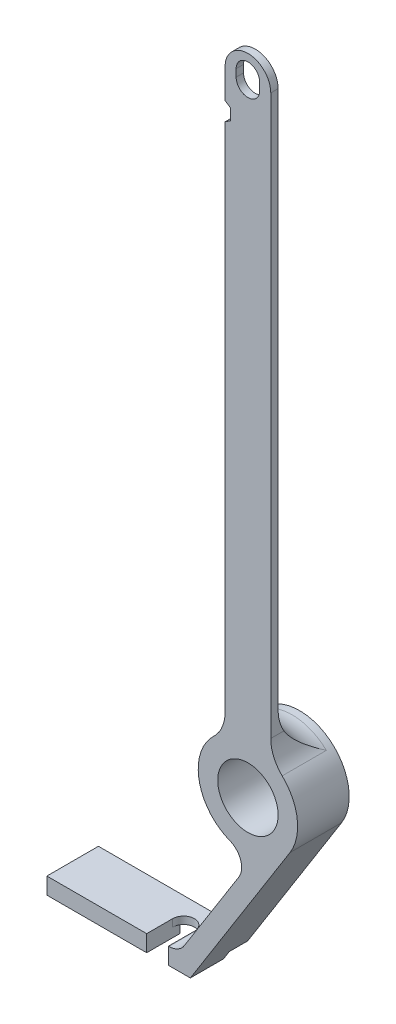
SolidWorks part; units mm, degrees
ref_plane "Front Plane" through (0, 0, 0) normal (0, 0, 1) x (1, 0, 0)
ref_plane "Top Plane" through (0, 0, 0) normal (0, 1, 0) x (1, 0, 0)
ref_plane "Right Plane" through (0, 0, 0) normal (1, 0, 0) x (0, 0, -1)
sketch "Sketch1" plane through (0, 0, 0) normal (0, 0, 1) x (1, 0, 0)
  line L0 (329.4964, 72.6482) -> (279.2958, 72.6482) construction
  line L1 (329.4964, 72.6482) -> (279.2958, 72.6482)
  line L2 (356.876, 116.1922) -> (329.4964, 72.6482)
  line L3 (279.2958, 72.6482) -> (279.2958, 77.6482)
  line L4 (279.2958, 77.6482) -> (326.7341, 77.6482)
  line L5 (347.0604, 109.9749) -> (326.7341, 77.6482)
  circle A2 centre (345.4475, 123.3782) radius 10.7
  circle A3 centre (345.4475, 123.3782) radius 10.7
  circle A5 centre (345.4475, 123.3782) radius 13.5
  circle A6 centre (345.4475, 123.3782) radius 13.5
  point P11 (321.6004, 79.1906)
  dimension "D3" = 5
  dimension "D4" = 5
  dimension "D1" = 0.2
  dimension "D2" = 3
extrude "Boss-Extrude1" add sketch "Sketch1" along normal blind 14 contours A6 L5 L4 L3 L1 L2 | A6 A3 region at (304.3961, 73.5378, 0) region at (352.467, 112.2961, 0)
sketch "Sketch2" plane through (0, 0, 14) normal (0, 0, 1) x (1, 0, 0)
  circle A1 centre (345.4475, 292.2362) radius 6.2
  arc A2 (348.6475, 292.2362) -> (345.3138, 289.039) centre (345.4475, 292.2362) ccw
  circle A3 centre (345.4475, 292.2362) radius 3.2
  point P0 (345.3789, 289.039)
  dimension "D1" = 0.2
  dimension "D2" = 3
extrude "Boss-Extrude2" add sketch "Sketch2" against normal blind 2 separate body
sketch "Sketch3" plane through (0, 0, 14) normal (0, 0, 1) x (1, 0, 0)
  line L0 (339.2475, 292.2362) -> (339.2475, 135.3703)
  line L1 (351.6475, 292.2362) -> (351.6475, 135.3703)
  line L2 (351.6475, 292.2362) -> (339.2475, 292.2362) construction
  circle A0 centre (345.4475, 292.2362) radius 6.2 construction
  arc A1 (356.876, 116.1922) -> (347.0604, 109.9749) centre (345.4475, 123.3782) ccw construction
  arc A2 (356.876, 116.1922) -> (347.0604, 109.9749) centre (345.4475, 123.3782) ccw
  circle A3 centre (345.4475, 292.2362) radius 6.2
  point P10 (339.307, 293.0933)
  circle M3 centre (345.4475, 292.2362) radius 6.2
extrude "Boss-Extrude3" add sketch "Sketch3" against normal blind 2 contours A2 L1 L0 M3 region at (345.4475, 211.8827, 14)
sketch "Sketch4" plane through (0, 0, 14) normal (0, 0, 1) x (1, 0, 0)
  line L0 (339.2475, 284.2362) -> (340.7475, 283.2362)
  line L1 (340.7475, 283.2362) -> (340.7475, 280.2362)
  line L2 (340.7475, 280.2362) -> (339.2475, 279.2362)
  line L3 (339.2475, 292.2362) -> (339.2475, 135.3703) construction
  line L4 (339.2475, 279.2362) -> (339.2475, 284.2362)
  circle A0 centre (345.4475, 292.2362) radius 3.2 construction
  point P2 (339.2475, 283.8537)
  dimension "D1" = 3
  dimension "D2" = 1.5
  dimension "D3" = 1
  dimension "D4" = 9
extrude "Cut-Extrude1" cut sketch "Sketch4" against normal blind 2
sketch "Sketch5" plane through (0, 77.6482, 0) normal (0, 1, 0) x (1, 0, 0)
  line L0 (284.9458, -6.9385) -> (284.9458, -16.0141)
  line L1 (284.9458, -16.0141) -> (290.8458, -16.0141)
  line L2 (290.8458, -16.0141) -> (290.8458, -6.9385)
  line L3 (317.9464, -6.9385) -> (317.9464, -18.3931)
  line L4 (317.9464, -18.3931) -> (323.8464, -18.3931)
  line L5 (323.8464, -18.3931) -> (323.8464, -6.9385)
  arc A2 (287.8958, -9.8885) -> (287.8958, -3.9885) centre (287.8958, -6.9385) ccw
  circle A3 centre (287.8958, -6.9385) radius 2.95
  arc A5 (320.8964, -9.8885) -> (320.8964, -3.9885) centre (320.8964, -6.9385) ccw
  circle A6 centre (320.8964, -6.9385) radius 2.95
  line M5 (279.2958, -14) -> (326.7341, -14)
  dimension "D1" = 0.2
  dimension "D2" = 0.2
extrude "Cut-Extrude2" cut sketch "Sketch5" against normal through all contours A6 L3 L5 M5 | A6 | A3 L0 L2 M5 | A3 region at (287.8958, 77.6482, 11.582) region at (320.8964, 77.6482, 11.582) region at (287.8958, 77.6482, 6.9385) region at (320.8964, 77.6482, 6.9385)
sketch "Sketch6" plane through (0, 0, 14) normal (0, 0, 1) x (1, 0, 0)
  circle A1 centre (345.4475, 123.3782) radius 10.7 construction
  circle A2 centre (345.4475, 123.3782) radius 8.2
  circle A3 centre (345.4475, 123.3782) radius 8.2
  circle A4 centre (345.4475, 123.3782) radius 10.7
  dimension "D1" = 0.2
extrude "Boss-Extrude4" add sketch "Sketch6" against normal blind 12.5
chamfer "Chamfer1" distance 1 angle 45 1 edges at (304.3961, 72.6482, 0)
fillet "Fillet1" radius 5 1 edges at (347.0604, 109.9749, 7)
fillet "Fillet2" radius 5 1 edges at (326.7341, 77.6482, 7)
fillet "Fillet3" radius 10 2 edges at (339.2475, 135.3703, 13) (351.6475, 135.3703, 13)
fillet "Fillet4" radius 10 1 edges at (345.4475, 136.8782, 12)
sketch "Sketch7" plane through (0, 77.6482, 0) normal (0, 1, 0) x (1, 0, 0)
  line L3 (280.9373, 5.0108) -> (268.5394, 0.9997)
  line L4 (268.5394, 0.9997) -> (269.8764, -16.5033)
  line L5 (269.8764, -16.5033) -> (286.4678, -20.2713)
  line L7 (290.8458, -6.9385) -> (290.8458, -19.413)
  line L8 (290.8458, -19.413) -> (286.4678, -20.2713)
  line L9 (290.8458, -6.9385) -> (290.8458, 6.0732)
  line L10 (290.8458, 6.0732) -> (280.9373, 5.0108)
  arc A0 (290.8458, -6.9385) -> (284.9458, -6.9385) centre (287.8958, -6.9385) ccw construction
  arc A1 (290.8458, -6.9385) -> (284.9458, -6.9385) centre (287.8958, -6.9385) ccw construction
extrude "Cut-Extrude3" cut sketch "Sketch7" against normal blind 10
sketch "Sketch9" plane through (0, 0, 0) normal (0, 0, -1) x (-1, 0, 0)
  line L0 (-290.8458, 72.6482) -> (-329.4964, 72.6482) construction
  line L1 (-336.7925, 75.6482) -> (-278.5683, 75.6482)
  line L2 (-336.7925, 75.6482) -> (-336.7925, 64.1138)
  line L3 (-336.7925, 64.1138) -> (-278.5683, 64.1138)
  line L4 (-278.5683, 75.6482) -> (-278.5683, 64.1138)
  dimension "D1" = 3
extrude "Cut-Extrude4" cut sketch "Sketch9" against normal blind 5
sketch "Sketch10" plane through (0, 72.6482, 0) normal (0, -1, 0) x (1, 0, 0)
  line L1 (278.6737, 21.3583) -> (380.3537, 21.3583)
  line L2 (278.6737, 21.3583) -> (278.6737, -6.605)
  line L3 (278.6737, -6.605) -> (380.3537, -6.605)
  line L4 (380.3537, 21.3583) -> (380.3537, -6.605)
extrude "Cut-Extrude5" cut sketch "Sketch10" against normal blind 0.5
sketch "Sketch11" plane through (0, 73.1482, 0) normal (0, -1, 0) x (1, 0, 0)
  line L1 (317.9464, 6.9385) -> (323.8464, 6.9385)
  line L2 (317.9464, 6.9385) -> (317.9464, -2.3502)
  line L3 (317.9464, -2.3502) -> (323.8464, -2.3502)
  line L4 (323.8464, 6.9385) -> (323.8464, -2.3502)
  point P4 (323.8464, 6.9385)
extrude "Cut-Extrude6" cut sketch "Sketch11" against normal up to surface (2.5 mm away) up to face at (314.375, 75.6482, 3.1648)
sketch "Sketch12" plane through (0, 0, 12) normal (0, 0, -1) x (-1, 0, 0)
  line L0 (-345.4475, 291.2362) -> (-345.4475, 293.2362) construction
  line L1 (-348.6475, 291.2362) -> (-348.6475, 293.2362)
  line L2 (-342.2475, 291.2362) -> (-342.2475, 293.2362)
  circle A0 centre (-345.4475, 292.2362) radius 3.2 construction
  circle A1 centre (-345.4475, 292.2362) radius 3.2 construction
  arc A2 (-348.6475, 291.2362) -> (-342.2475, 291.2362) centre (-345.4475, 291.2362) ccw
  arc A3 (-342.2475, 293.2362) -> (-348.6475, 293.2362) centre (-345.4475, 293.2362) ccw
  point P5 (-345.4475, 292.2362)
  dimension "D1" = 1
extrude "Cut-Extrude7" cut sketch "Sketch12" against normal through all
